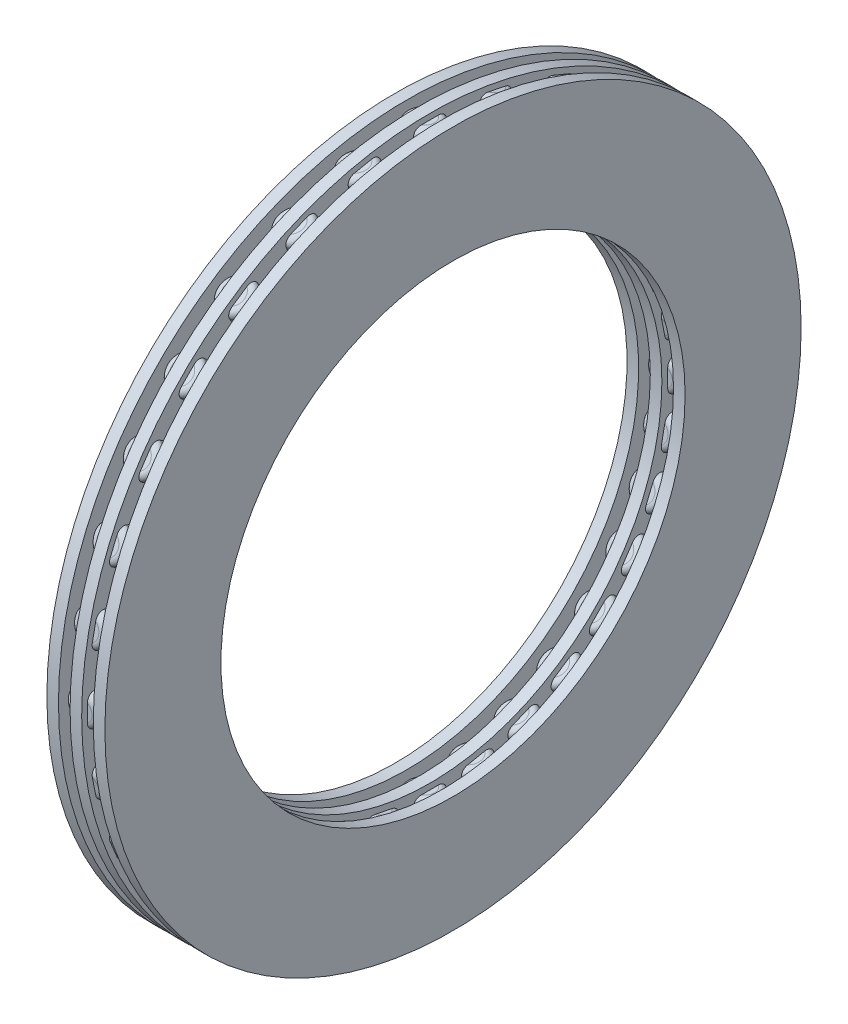
SolidWorks part; units mm, degrees
ref_plane "Plane1" through (0, 0, 0) normal (0, 0, 1) x (1, 0, 0)
ref_plane "Plane2" through (0, 0, 0) normal (0, 1, 0) x (1, 0, 0)
ref_plane "Plane3" through (0, 0, 0) normal (1, 0, 0) x (0, 0, -1)
sketch "Clipboard" plane through (0, 0, 0) normal (0, 0, 1) x (1, 0, 0)
  line L0 (-10, 0) -> (10, 0) construction
  line L1 (0, 0) -> (18.9629, -11.8494)
  line L2 (0, 0) -> (21.2012, 13.248)
  line L3 (0, 0) -> (18.9629, -11.8494)
  line L4 (0, 0) -> (-22.3471, -0.7804)
  dimension "BallCLRad" = 25
sketch "CagSpiSke" plane through (0, 0, 0) normal (0, 0, 1) x (1, 0, 0)
  line L5 (-34.925, 0) -> (34.925, 0) construction
  line L6 (-0.5, 30) -> (0.5, 30)
  line L7 (-0.5, 30) -> (-0.5, 20)
  line L8 (-0.5, 20) -> (0.5, 20)
  line L9 (0.5, 30) -> (0.5, 20)
  dimension "ID" = 40
  dimension "OD" = 60
revolve "CageSpine" add sketch "CagSpiSke" angle 360 about L5 reverse direction yes
ref_axis "Axis1" through (-50, 0, 0) along (1, 0, 0)
sketch "RolDetSke" plane through (0, 0, 0) normal (0, 0, 1) x (1, 0, 0)
  line L0 (0, 33.02) -> (0, 55.88) construction
  line L3 (0, 29.5) -> (0.9, 29.5)
  line L4 (0, 29.5) -> (0, 20.5)
  line L5 (0, 20.5) -> (0.9, 20.5)
  line L6 (1.5, 28.9) -> (1.5, 21.1)
  arc A0 (1.5, 21.1) -> (0.9, 20.5) centre (0.9, 21.1) cw
  arc A1 (0.9, 29.5) -> (1.5, 28.9) centre (0.9, 28.9) cw
  dimension "offset" = 20.5
  dimension "Roller_diameter" = 3
  dimension "Cyl_Len" = 9
revolve "RollerDetailed" add sketch "RolDetSke" angle 360 about L0 reverse direction yes
pattern_circular "RollersDetailed" count 32 every 11.25 about axis through (-50, 0, 0) along (1, 0, 0) of "RollerDetailed"
sketch "RolSimSke" plane through (0, 0, 0) normal (0, 0, 1) x (1, 0, 0)
  line L1 (-17.78, 0) -> (12.7, 0) construction
  line L3 (-0.9, 29.5) -> (0.9, 29.5)
  line L4 (-1.5, 28.9) -> (-1.5, 21.1)
  line L5 (-0.9, 20.5) -> (0.9, 20.5)
  line L6 (1.5, 28.9) -> (1.5, 21.1)
  arc A0 (-1.5, 21.1) -> (-0.9, 20.5) centre (-0.9, 21.1) ccw
  arc A1 (-0.9, 29.5) -> (-1.5, 28.9) centre (-0.9, 28.9) ccw
  arc A2 (1.5, 28.9) -> (0.9, 29.5) centre (0.9, 28.9) ccw
  arc A3 (0.9, 20.5) -> (1.5, 21.1) centre (0.9, 21.1) ccw
  dimension "Halfdia" = 1.5
  dimension "offset" = 20.5
  dimension "Roller_diameter" = 3
  dimension "Cyl_Len" = 9
ref_plane "Plane4" through (1.5, 0, 0) normal (1, 0, 0) x (0, 0, -1)
sketch "Sketch1" plane through (1.5, 0, 0) normal (1, 0, 0) x (0, 0, -1)
  circle A0 centre (0, 0) radius 30
  circle A1 centre (0, 0) radius 20
extrude "Boss-Extrude1" add sketch "Sketch1" along normal blind 1 separate body
ref_plane "Plane5" through (-1.5, 0, 0) normal (-1, 0, 0) x (0, 0, 1)
sketch "Sketch2" plane through (-1.5, 0, 0) normal (-1, 0, 0) x (0, 0, 1)
  circle A0 centre (0, 0) radius 30
  circle A2 centre (0, 0) radius 20
extrude "Boss-Extrude2" add sketch "Sketch2" along normal blind 1 separate body
equation "\"BallCLRad@Clipboard\" =  ( \"OD@CagSpiSke\" + \"ID@CagSpiSke\" )  / 4"
equation "\"offset@RolSimSke\" = \"BallCLRad@Clipboard\" - \"Cyl_Len@RolSimSke\" / 2"
equation "\"offset@RolDetSke\" = \"BallCLRad@Clipboard\" - \"Cyl_Len@RolDetSke\" / 2"
equation "\"Thickness@CagSpiSke\" =  \"Roller_diameter@RolDetSke\"  / 3"
equation "\"HalfThick@CagSpiSke\" = \"Thickness@CagSpiSke\" / 2"
equation "\"radius@RolDetSke\" =  ( \"Roller_diameter@RolDetSke\" - \"Thickness@CagSpiSke\" )  * 0.6 / 2"
equation "\"Roller_diameter@RolSimSke\" = \"Roller_diameter@RolDetSke\""
equation "\"Cyl_Len@RolSimSke\" = \"Cyl_Len@RolDetSke\""
equation "\"Rol_rad@RolSimSke\" = \"radius@RolDetSke\""
equation "\"Halfdia@RolSimSke\" = \"Roller_diameter@RolSimSke\" / 2"
equation "\"Max_count@Clipboard\" = int( 3.14159265 / atn(( \"Roller_diameter@RolDetSke\" / 2) / sqr( \"offset@RolDetSke\"  *  \"offset@RolDetSke\" - ( \"Roller_diameter@RolDetSke\" / 2) *  ( \"Roller_diameter@RolDetSke\" / 2))))"
equation "\"Max_count@Clipboard\" = ((sgn( \"Max_count@Clipboard\" - \"Count@Clipboard\" )-1)*( \"Max_count@Clipboard\" - \"Count@Clipboard\" ))/-2+ \"Count@Clipboard\""
equation "\"Count@RollersDetailed\" = int( \"Show_count@Clipboard\" ) "
equation "\"Count@RollersDetailed\" = ((sgn( \"Count@RollersDetailed\" - \"Max_count@Clipboard\" )-1)*( \"Count@RollersDetailed\" - \"Max_count@Clipboard\" ))/-2+ \"Max_count@Clipboard\""
equation "\"Count@RollersDetailed\" = ((sgn( \"Count@RollersDetailed\" - \"Min_count@Clipboard\" )+1)*( \"Count@RollersDetailed\" - \"Min_count@Clipboard\"))/2 +\"Min_count@Clipboard\""
equation "\"Angle@RollersDetailed\" = 360.0 / \"Max_count@Clipboard\""
